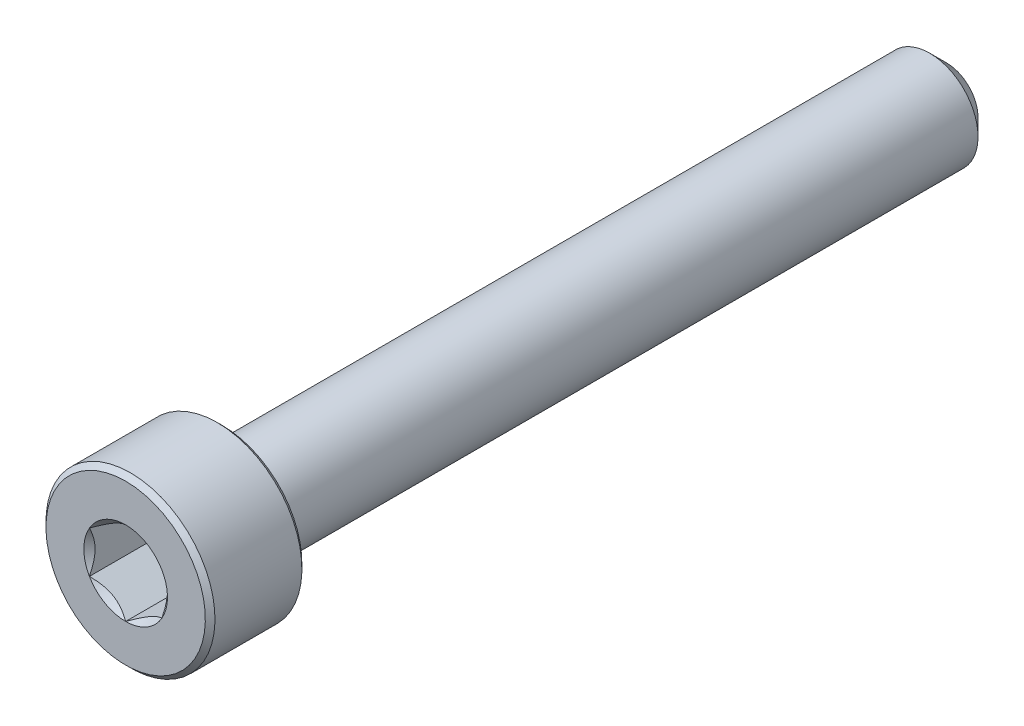
SolidWorks part; units mm, degrees
ref_plane "Front Plane" through (0, 0, 0) normal (0, 0, 1) x (1, 0, 0)
ref_plane "Top Plane" through (0, 0, 0) normal (0, 1, 0) x (1, 0, 0)
ref_plane "Right Plane" through (0, 0, 0) normal (1, 0, 0) x (0, 0, -1)
sketch "Sketch1" plane through (0, 0, 0) normal (1, 0, 0) x (0, 0, -1)
  line L0 (-17, 0) -> (17, 0) construction
  line L1 (17, 0) -> (17, 1.3) construction
  line L2 (17, 1.3) -> (16.3, 2) construction
  line L3 (16.3, 2) -> (16.475, 2) construction
  line L4 (16.475, 2) -> (-13, 2) construction
  line L5 (-13, 2) -> (-13, 3.5) construction
  line L6 (-13, 3.5) -> (-17, 3.5) construction
  line L7 (-17, 3.5) -> (-17, 0) construction
  line L8 (17, 1.3) -> (17, 2) construction
  line L9 (16.9563, 2.0758) -> (17.3063, 1.4696) construction
  line L10 (17.3063, 1.4696) -> (17.6563, 2.0758) construction
  line L11 (17.6563, 2.0758) -> (16.9563, 2.0758) construction
  line L12 (17.3063, 2.0758) -> (17.3063, 2) construction
  line L13 (17.3063, 1.4696) -> (17.3063, 1.5453) construction
  line L14 (17.2625, 1.5453) -> (17.35, 1.5453) construction
  line L15 (17, 2) -> (17.6125, 2) construction
  line L16 (16.9781, 2.0379) -> (17.6344, 2.0379) construction
  line L17 (17, 0) -> (17, -2) construction
  line L18 (-13.2, 3.5) -> (-13, 3.3) construction
  line L19 (-16.8, 3.5) -> (-17, 3.3) construction
  line L20 (-13, 2) -> (-13, 0) construction
  line L21 (-13, 1) -> (-3, 1) construction
  line L22 (-3, 1) -> (7, 1) construction
  line L23 (7, 1) -> (17, 1) construction
  line L24 (-3, 1) -> (-3, 2) construction
  line L25 (-3, 2) -> (-3, 3.5) construction
  line L26 (7, 1) -> (7, 3.5) construction
  point P0 (-17, 1.5)
  point P3 (15.25, 2)
  point P4 (0, 0)
  point P18 (7, 2)
  point P22 (17.3063, 1.5453)
  point P24 (16.475, 2)
  point P25 (17.3063, 2)
  point P28 (17.3063, 2.0379)
  point P29 (15.25, -2)
  point P30 (-3, 2)
  point P31 (-15, 3.5)
  point P37 (-13.7, 3.5)
  point P38 (-16.7, 3.5)
  point P45 (-3, 1)
  point P46 (7, 1)
  dimension "D1" = 45
  dimension "D2" = 0.0875
  dimension "D3" = 0.7
  dimension "D7" = 0.2
  dimension "D8" = 0.2
  dimension "D9" = 0.2
  dimension "D10" = 0.1
  dimension "D11" = 0.5
  dimension "Drive Size" = 3
  dimension "Head Diameter" = 7
  dimension "Head Height" = 4
  dimension "Thread Pitch" = 0.7
  dimension "Thread Major Diameter" = 4
  dimension "Length" = 30
  dimension "D12" = 0.525
  dimension "D4" = 1.75
sketch "Sketch2" plane through (0, 0, 0) normal (1, 0, 0) x (0, 0, -1)
  line L0 (-17, 0) -> (-17, 3.3)
  line L1 (-16.8, 3.5) -> (-13.2, 3.5)
  line L2 (-13, 3.3) -> (-13, 2)
  line L3 (-13, 2) -> (16.3, 2)
  line L4 (16.3, 2) -> (17, 1.3)
  line L5 (17, 1.3) -> (17, 0)
  line L6 (-13.2, 3.5) -> (-13, 3.3) construction
  line L7 (17, 0) -> (-17, 0)
  line L8 (-16.8, 3.5) -> (-17, 3.3) construction
  line L9 (-13.2, 3.5) -> (-13, 3.3)
  line L10 (-16.8, 3.5) -> (-17, 3.3)
revolve "Revolve1" add sketch "Sketch2" angle 360 about L7
sketch "Sketch3" plane through (0, 0, 17) normal (0, 0, 1) x (1, 0, 0)
  line L1 (1.5, -0.866) -> (1.5, 0.866)
  line L2 (1.5, 0.866) -> (0, 1.7321)
  line L3 (0, 1.7321) -> (-1.5, 0.866)
  line L4 (-1.5, 0.866) -> (-1.5, -0.866)
  line L5 (-1.5, -0.866) -> (0, -1.7321)
  line L6 (0, -1.7321) -> (1.5, -0.866)
  circle A0 centre (0, 0) radius 1.5 construction
extrude "Cut-Extrude1" cut sketch "Sketch3" against normal offset from surface (3 mm away) 1 up to face at (0, 3.3, 13)
sketch "Sketch4" plane through (0, 0, 17) normal (0, 0, 1) x (1, 0, 0)
  circle A0 centre (0, 0) radius 1.7321
extrude "Cut-Extrude2" cut sketch "Sketch4" against normal up to vertex (2 mm away) draft 45 up to point (0, 3.5, 15)
ref_plane "Plane1" [suppressed] through (0, 0, -16.475) normal (0, 0, 1) x (1, 0, 0)
split "Split1" [suppressed] bodies to split 106
sketch "Sketch6" [suppressed] plane through (0, 0, -17) normal (0, 0, -1) x (-1, 0, 0)
  circle A0 centre (0, 0) radius 2
curve "Helix/Spiral1" [suppressed] pitch 0.7 height 30.805 turns 44.0071
sketch "Sketch7" [suppressed] plane through (0, 0, 0) normal (1, 0, 0) x (0, 0, -1)
  line L0 (16.9781, 2.0379) -> (17.6344, 2.0379)
  line L1 (17.6344, 2.0379) -> (17.35, 1.5453)
  line L2 (17.35, 1.5453) -> (17.2625, 1.5453)
  line L3 (17.2625, 1.5453) -> (16.9781, 2.0379)
sweep "Cut-Sweep1" [suppressed] cut profiles "Sketch7" path "Helix/Spiral1"
sketch "Sketch8" [suppressed] plane through (0, 0, 13) normal (0, 0, -1) x (-1, 0, 0)
  circle A0 centre (0, 0) radius 2
extrude "Boss-Extrude1" [suppressed] add sketch "Sketch8" along normal through all draft 45
equation "\"D2@Sketch1\" = \"Thread Pitch@Sketch1\" / 8"
equation "\"D3@Sketch1\"= \"Thread Pitch@Sketch1\""
equation "\"D4@Helix/Spiral1\" = \"Thread Pitch@Sketch1\""
equation "\"D7@Sketch1\" = \"Head Height@Sketch1\" * .05"
equation "\"D8@Sketch1\"=\"D7@Sketch1\""
equation "\"D9@Sketch1\"=\"D7@Sketch1\""
equation "\"D10@Sketch1\"=\"D7@Sketch1\"/2"
equation "\"D11@Sketch1\"=\"D10@Sketch1\"*5"
equation "\"D4@Sketch1\"=\"Thread Pitch@Sketch1\"*2.5"
equation "\"D12@Sketch1\"=\"Thread Pitch@Sketch1\"*.75"
